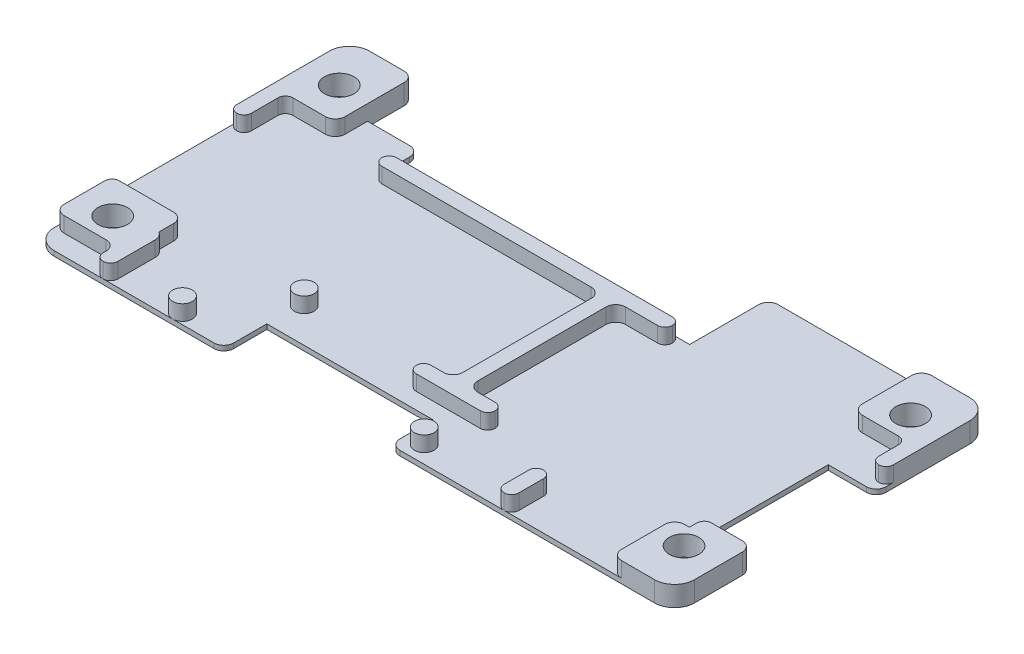
SolidWorks part; units mm, degrees
ref_plane "Front Plane" through (0, 0, 0) normal (0, 0, 1) x (1, 0, 0)
ref_plane "Top Plane" through (0, 0, 0) normal (0, 1, 0) x (1, 0, 0)
ref_plane "Right Plane" through (0, 0, 0) normal (1, 0, 0) x (0, 0, -1)
sketch "Sketch1" plane through (0, -3.35, 0) normal (0, -1, 0) x (1, 0, 0)
  line L4 (-30.4681, -16.0016) -> (30.4681, -16.0016)
  line L5 (32.5001, -13.9696) -> (32.5001, 13.9696)
  line L6 (30.4681, 16.0016) -> (-30.4681, 16.0016)
  line L7 (-32.5001, 13.9696) -> (-32.5001, -13.9696)
  line L8 (-30.4681, -16.0016) -> (30.4681, -16.0016)
  line L9 (32.5001, -13.9696) -> (32.5001, 13.9696)
  line L10 (30.4681, 16.0016) -> (-30.4681, 16.0016)
  line L11 (-32.5001, 13.9696) -> (-32.5001, -13.9696)
  circle A0 centre (28.9999, -11.4637) radius 1.5 construction
  circle A1 centre (28.9999, 11.5363) radius 1.5 construction
  circle A2 centre (-29.0002, -11.4637) radius 1.5 construction
  circle A3 centre (-29.0002, 11.5363) radius 1.5 construction
  arc A4 (-32.5001, -13.9696) -> (-30.4681, -16.0016) centre (-30.4681, -13.9696) ccw
  arc A5 (30.4681, -16.0016) -> (32.5001, -13.9696) centre (30.4681, -13.9696) ccw
  arc A6 (32.5001, 13.9696) -> (30.4681, 16.0016) centre (30.4681, 13.9696) ccw
  arc A7 (-30.4681, 16.0016) -> (-32.5001, 13.9696) centre (-30.4681, 13.9696) ccw
  arc A8 (-32.5001, -13.9696) -> (-30.4681, -16.0016) centre (-30.4681, -13.9696) ccw
  arc A9 (30.4681, -16.0016) -> (32.5001, -13.9696) centre (30.4681, -13.9696) ccw
  arc A10 (32.5001, 13.9696) -> (30.4681, 16.0016) centre (30.4681, 13.9696) ccw
  arc A11 (-30.4681, 16.0016) -> (-32.5001, 13.9696) centre (-30.4681, 13.9696) ccw
  circle A12 centre (28.9999, -11.4637) radius 1.5
  circle A13 centre (28.9999, 11.5363) radius 1.5
  circle A14 centre (-29.0002, -11.4637) radius 1.5
  circle A15 centre (-29.0002, 11.5363) radius 1.5
  dimension "D1" = 0
extrude "Boss-Extrude1" add sketch "Sketch1" against normal blind 0.5
sketch "Sketch2" plane through (0, -3.35, 0) normal (0, -1, 0) x (1, 0, 0)
  line L0 (-13.2479, 11.6407) -> (3.6238, 11.6407) construction
  line L1 (-13.2479, 11.6407) -> (3.6238, 11.6407)
  line L2 (-13.2479, 11.6407) -> (-13.2479, 16.0016)
  line L3 (-13.2479, 16.0016) -> (3.6238, 16.0016)
  line L4 (3.6238, 11.6407) -> (3.6238, 16.0016)
  line L5 (-30.4681, 16.0016) -> (30.4681, 16.0016) construction
  line L7 (-30.4681, -16.0016) -> (30.4681, -16.0016) construction
  line L8 (-20.6686, -8.0016) -> (10.0286, -8.0016)
  line L9 (-20.6686, -8.0016) -> (-20.6686, -11.28)
  line L10 (-25.9446, -16.0016) -> (10.0286, -16.0016)
  line L11 (10.0286, -8.0016) -> (10.0286, -16.0016)
  line L12 (-25.6946, -11.58) -> (-25.6946, -14.28) construction
  line L13 (-25.9446, -11.28) -> (-20.6686, -11.28)
  line L14 (-25.9446, -11.28) -> (-25.9446, -16.0016)
  line L20 (32.5001, -13.9696) -> (32.5001, 13.9696) construction
  line L21 (27.6311, 8.1251) -> (32.5001, 8.1251)
  line L22 (27.6311, 8.1251) -> (27.6311, -4.4749)
  line L23 (27.6311, -4.4749) -> (32.5001, -4.4749)
  line L24 (32.5001, 8.1251) -> (32.5001, -4.4749)
  line L27 (-21.0144, -11.58) -> (-25.6946, -11.58) construction
  line L28 (-20.4186, -9.5016) -> (-20.4186, -15.5016) construction
  line L29 (9.7786, -15.5016) -> (9.7786, -9.5016) construction
  line L30 (32.3812, 7.8751) -> (27.8811, 7.8751) construction
  line L31 (27.8811, -4.2249) -> (32.3812, -4.2249) construction
  line L32 (27.8811, 7.8751) -> (27.8811, -4.2249) construction
  dimension "D1" = 0.25
  dimension "D2" = 0.3
  dimension "D3" = 8
  dimension "D4" = 0.25
  dimension "D5" = 0.25
  dimension "D6" = 0.25
  dimension "D7" = 0.25
  dimension "D8" = 0.25
extrude "Cut-Extrude2" cut sketch "Sketch2" against normal through all
fillet "Fillet1" radius 1 7 edges at (3.6238, -3.1, 16.0016) (-13.2479, -3.1, 16.0016) (-20.6686, -3.1, -11.28) (-25.9446, -3.1, -16.0016) (10.0286, -3.1, -16.0016) (32.5001, -3.1, -4.4749) (32.5001, -3.1, 8.1251)
sketch "Sketch3" plane through (0, -3.35, 0) normal (0, -1, 0) x (1, 0, 0)
  line L0 (10.0286, -8.0016) -> (-20.6686, -8.0016) construction
  line L1 (-20.4686, -8.0016) -> (9.0286, -8.0016)
  line L2 (-20.4686, -8.0016) -> (-20.4686, -6.5016)
  line L3 (-20.4686, -6.5016) -> (2.5286, -6.5016)
  line L4 (9.0286, -8.0016) -> (9.0286, -6.5016)
  line L5 (-30.4681, -16.0016) -> (-26.9446, -16.0016) construction
  line L6 (-0.4714, 9.9984) -> (7.5286, 9.9984)
  line L7 (10.0286, -15.0016) -> (10.0286, -8.0016) construction
  line L8 (-0.4714, 9.9984) -> (-0.4714, 8.4984)
  line L9 (-0.4714, 8.4984) -> (2.5286, 8.4984)
  line L10 (7.5286, 9.9984) -> (7.5286, 8.4984)
  line L11 (14.4541, 16.0016) -> (15.9541, 16.0016)
  line L12 (14.4541, 16.0016) -> (14.4541, 12.0016)
  line L13 (14.4541, 12.0016) -> (15.9541, 12.0016)
  line L14 (15.9541, 16.0016) -> (15.9541, 12.0016)
  line L15 (3.6238, 14.269) -> (5.3565, 14.269) construction
  line L16 (-32.5001, -3.7972) -> (-32.5001, -13.9696)
  line L17 (-25.9446, -8.0016) -> (-31.0001, -8.0016)
  line L18 (-31.0001, -8.0016) -> (-31.0001, -3.7972)
  line L19 (-31.0001, -3.7972) -> (-32.5001, -3.7972)
  line L20 (32.5001, -5.4749) -> (31.0001, -5.4749)
  line L21 (31.0001, -5.4749) -> (31.0001, -9.0016)
  line L22 (4.0286, -6.5016) -> (9.0286, -6.5016)
  line L28 (2.5286, 8.4984) -> (2.5286, -6.5016)
  line L30 (4.0286, 8.4984) -> (4.0286, -6.5016)
  line L31 (4.0286, 8.4984) -> (7.5286, 8.4984)
  line L32 (-32.5001, 13.9696) -> (-32.5001, -13.9696) construction
  line L33 (-32.4001, -3.4972) -> (-21.1001, -3.4972) construction
  line L34 (-30.4681, -16.0016) -> (30.4681, -16.0016) construction
  line L35 (-25.9446, -8.0016) -> (-25.9446, -15.0016)
  line L36 (-30.4681, -16.0016) -> (-26.9446, -16.0016)
  line L37 (31.0001, -9.0016) -> (25.5692, -9.0016)
  line L38 (25.3192, -15.9483) -> (25.3192, -5.0329) construction
  line L39 (32.5001, -5.4749) -> (32.5001, -13.9696)
  line L40 (25.5692, -9.0016) -> (25.5692, -16.0016)
  line L41 (11.0286, -16.0016) -> (30.4681, -16.0016) construction
  line L42 (32.5001, -13.9696) -> (32.5001, -5.4749) construction
  line L43 (25.5692, -16.0016) -> (30.4681, -16.0016)
  line L44 (27.6311, 8.1251) -> (27.6311, 9.6251)
  line L45 (27.6311, 9.6251) -> (26.1311, 9.6251)
  line L46 (26.1311, 9.6251) -> (26.1311, 16.0016)
  line L47 (30.4681, 16.0016) -> (4.6238, 16.0016) construction
  line L48 (26.1311, 16.0016) -> (30.4681, 16.0016)
  line L49 (32.5001, 9.1251) -> (32.5001, 13.9696) construction
  line L50 (31.5001, 8.1251) -> (27.6311, 8.1251) construction
  line L51 (32.5001, 9.1251) -> (32.5001, 13.9696)
  line L52 (31.5001, 8.1251) -> (27.6311, 8.1251)
  line L53 (3.6238, 11.6407) -> (3.6238, 15.2251) construction
  line L54 (5.3565, 14.269) -> (7.0891, 14.269) construction
  line L55 (7.0891, 14.7928) -> (7.0891, 12.073) construction
  line L56 (5.3565, 14.269) -> (5.3565, 16.0016) construction
  line L57 (13.4196, 17.3016) -> (16.9885, 17.3016) construction
  line L58 (16.9885, 17.3016) -> (16.9885, 17.0016) construction
  line L59 (15.2041, 16.0016) -> (15.2041, 17.3016) construction
  line L61 (-13.2479, 15.0016) -> (-13.2479, 11.6407) construction
  line L62 (-13.2479, 11.6407) -> (3.6238, 11.6407) construction
  line L63 (-14.2479, 16.0016) -> (-30.4681, 16.0016) construction
  line L64 (-13.2479, 15.2251) -> (-13.2479, 11.6407) construction
  line L65 (-32.5001, 8.1028) -> (-25.2501, 8.1028)
  line L66 (-24.7501, 10.6028) -> (-24.7501, 16.0016)
  line L67 (-32.5001, 8.1028) -> (-32.5001, 12.9587)
  line L70 (-21.1001, 7.8028) -> (-32.4001, 7.8028) construction
  line L71 (-26.975, 13.9587) -> (-31.5001, 13.9587) construction
  line L72 (-26.2501, 13.9587) -> (-31.5001, 13.9587)
  line L73 (-26.2501, 13.9587) -> (-26.2501, 16.0016)
  line L74 (-26.2501, 16.0016) -> (-24.7501, 16.0016)
  line L75 (-24.7501, 10.6028) -> (-25.2501, 10.6028)
  line L76 (-25.2501, 10.6028) -> (-25.2501, 8.1028)
  line L77 (10.0286, -14.5016) -> (11.5286, -14.5016) construction
  line L78 (11.5286, -14.5016) -> (11.5286, -16.0016) construction
  line L79 (10.0286, -15.0016) -> (10.0286, -14.5016) construction
  line L80 (11.0286, -16.0016) -> (11.5286, -16.0016) construction
  circle A0 centre (-12.9479, 8.1407) radius 1
  circle A1 centre (-18.4479, 15.0016) radius 1
  circle A3 centre (-29.0002, -11.4637) radius 1.5 construction
  arc A4 (-32.5001, -13.9696) -> (-30.4681, -16.0016) centre (-30.4681, -13.9696) ccw construction
  arc A5 (-26.9446, -16.0016) -> (-25.9446, -15.0016) centre (-26.9446, -15.0016) ccw construction
  circle A6 centre (-29.0002, -11.4637) radius 1.5
  arc A7 (-32.5001, -13.9696) -> (-30.4681, -16.0016) centre (-30.4681, -13.9696) ccw
  arc A8 (-26.9446, -16.0016) -> (-25.9446, -15.0016) centre (-26.9446, -15.0016) ccw
  arc A9 (30.4681, -16.0016) -> (32.5001, -13.9696) centre (30.4681, -13.9696) ccw construction
  arc A10 (30.4681, -16.0016) -> (32.5001, -13.9696) centre (30.4681, -13.9696) ccw
  circle A11 centre (28.9999, -11.4637) radius 1.5 construction
  circle A12 centre (28.9999, -11.4637) radius 1.5
  arc A13 (32.5001, 13.9696) -> (30.4681, 16.0016) centre (30.4681, 13.9696) ccw construction
  arc A14 (31.5001, 8.1251) -> (32.5001, 9.1251) centre (31.5001, 9.1251) ccw construction
  arc A15 (32.5001, 13.9696) -> (30.4681, 16.0016) centre (30.4681, 13.9696) ccw
  arc A16 (31.5001, 8.1251) -> (32.5001, 9.1251) centre (31.5001, 9.1251) ccw
  circle A17 centre (28.9999, 11.5363) radius 1.5 construction
  circle A18 centre (28.9999, 11.5363) radius 1.5
  circle A19 centre (5.3565, 14.269) radius 1
  circle A22 centre (-29.0002, 11.5363) radius 1.5 construction
  circle A23 centre (-29.0002, 11.5363) radius 1.5
  arc A25 (-31.5001, 13.9587) -> (-32.5001, 12.9587) centre (-31.5001, 12.9587) ccw construction
  arc A26 (10.0286, -15.0016) -> (11.0286, -16.0016) centre (11.0286, -15.0016) ccw construction
  arc A27 (-31.5001, 13.9587) -> (-32.5001, 12.9587) centre (-31.5001, 12.9587) ccw
  arc A28 (10.0286, -15.0016) -> (11.0286, -16.0016) centre (11.0286, -15.0016) ccw construction
  dimension "D8" = 1.5
  dimension "D17" = 2
  dimension "D1" = 0.2
  dimension "D2" = 1
  dimension "D3" = 1.5
  dimension "D4" = 1.5
  dimension "D5" = 8
  dimension "D6" = 1.5
  dimension "D7" = 4
  dimension "D9" = 1.5
  dimension "D10" = 0.3
  dimension "D11" = 1.5
  dimension "D12" = 8
  dimension "D13" = 7
  dimension "D14" = 0.25
  dimension "D15" = 1.5
  dimension "D16" = 1.5
  dimension "D18" = 0.3
  dimension "D19" = 3.5
  dimension "D20" = 5.2
  dimension "D21" = 6.25
  dimension "D22" = 0.3
  dimension "D23" = 5
  dimension "D24" = 15
  dimension "D25" = 3.5
  dimension "D26" = 1.5
  dimension "D27" = 0.5
  dimension "D28" = 2.5
  dimension "D29" = 1.5
extrude "Boss-Extrude2" add sketch "Sketch3" against normal up to surface (2.05 mm away)
fillet "Fillet2" radius 1 12 edges at (-25.9446, -2.075, -8.0016) (25.5692, -2.075, -16.0016) (25.5692, -2.075, -9.0016) (4.0286, -2.075, -6.5016) (2.5286, -2.075, -6.5016) (2.5286, -2.075, 8.4984) (4.0286, -2.075, 8.4984) (-24.7501, -2.075, 10.6028) (-26.2501, -2.075, 13.9587) (26.1311, -2.075, 16.0016) (26.1311, -2.075, 9.6251) (-25.2501, -2.075, 8.1028)
fillet "Fillet4" radius 0.75 22 edges at (-31.0001, -2.075, -8.0016) (-20.4686, -2.075, -8.0016) (-20.4686, -2.075, -6.5016) (-0.4714, -2.075, 8.4984) (-0.4714, -2.075, 9.9984) (7.5286, -2.075, 9.9984) (7.5286, -2.075, 8.4984) (9.0286, -2.075, -8.0016) (9.0286, -2.075, -6.5016) (31.0001, -2.075, -9.0016) (31.0001, -2.075, -5.4749) (32.5001, -2.075, -5.4749) (27.6311, -2.075, 8.1251) (14.4541, -2.075, 12.0016) (15.9541, -2.075, 12.0016) (15.9541, -2.075, 16.0016) (14.4541, -2.075, 16.0016) (-32.5001, -2.075, 8.1028) (-24.7501, -2.075, 16.0016) (-26.2501, -2.075, 16.0016) (-31.0001, -2.075, -3.7972) (-32.5001, -2.075, -3.7972)
